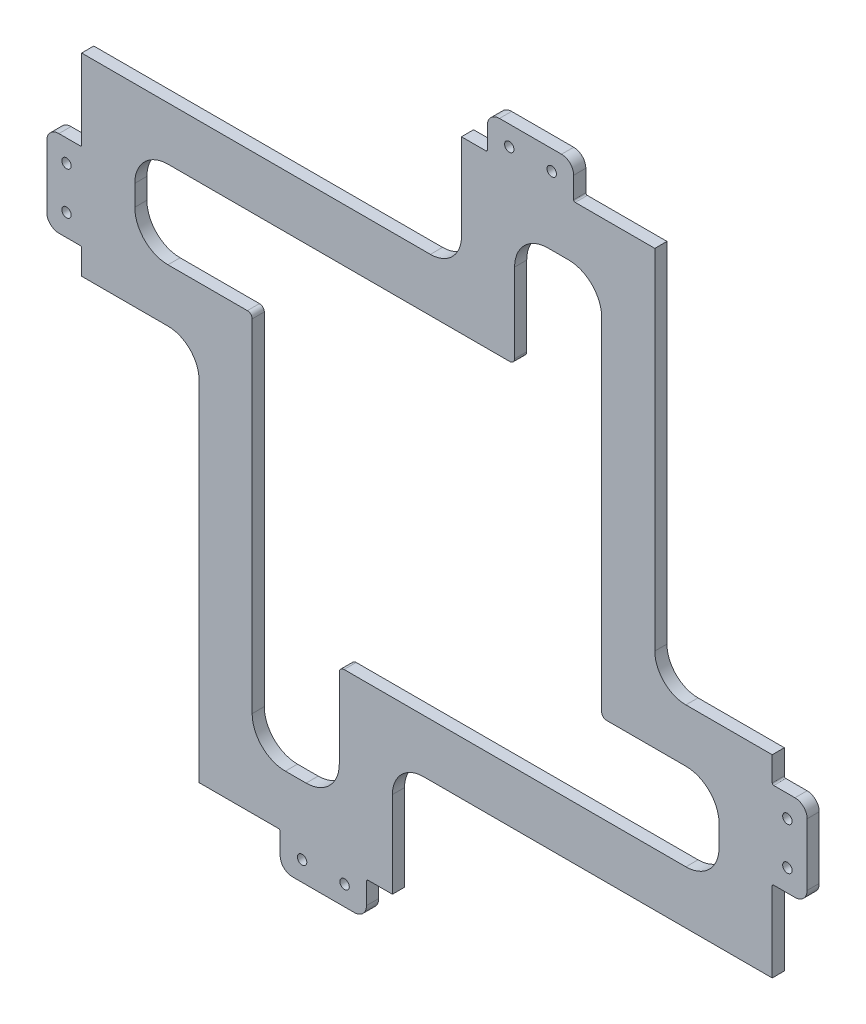
SolidWorks part; units mm, degrees
ref_plane "front" through (0, 0, 0) normal (0, 0, 1) x (1, 0, 0)
ref_plane "top" through (0, 0, 0) normal (0, 1, 0) x (1, 0, 0)
ref_plane "right" through (0, 0, 0) normal (1, 0, 0) x (0, 0, -1)
ref_axis "Axis1" through (0, 0, -69.7337) along (0, 0, 1)
sketch "Sketch1" plane through (0, 0, 0) normal (0, 0, 1) x (1, 0, 0)
  line L0 (-14.4526, 14.4526) -> (14.4526, 14.4526)
  line L1 (14.4526, 14.4526) -> (14.4526, -14.4526)
  line L2 (14.4526, -14.4526) -> (-14.4526, -14.4526)
  line L3 (-14.4526, -14.4526) -> (-14.4526, 14.4526)
  line L4 (-14.4526, 0) -> (-165.194, 0) construction
  line L5 (-165.194, 0) -> (0, 29.1282)
  line L6 (-165.194, 0) -> (0, 14.4526)
  dimension "D1" = 10
  dimension "D2" = 5
  dimension "D3" = 165.194
  dimension "D4" = 167.7424
  dimension "A" = 28.9052
sketch "Sketch2" plane through (0, 0, 0) normal (0, 0, 1) x (1, 0, 0)
  line L0 (-11.5621, 14.4526) -> (6.9372, 14.4526)
  line L1 (-14.4526, 14.4526) -> (14.4526, 14.4526) construction
  line L2 (7.5154, 15.0307) -> (7.5154, 21.6789)
  line L3 (14.4526, 21.6789) -> (14.4526, 5.781)
  line L4 (14.4526, 5.781) -> (19.0774, 5.781)
  line L5 (19.0774, 5.781) -> (19.0774, 28.9052)
  line L6 (4.9314, 28.9052) -> (2.8905, 28.9052)
  line L7 (2.8905, 21.6789) -> (7.5154, 21.6789) construction
  line L8 (2.8905, 28.9052) -> (2.8905, 21.6789)
  line L10 (19.0774, 28.9052) -> (12.4117, 28.9052)
  line L11 (12.2847, 29.0322) -> (12.2847, 30.8102)
  line L12 (11.2687, 31.8262) -> (6.0744, 31.8262)
  line L13 (5.0584, 30.8102) -> (5.0584, 29.0322)
  line L14 (0.2891, 19.0774) -> (-11.5621, 19.0774)
  line L15 (-11.5621, 19.0774) -> (-11.5621, 14.4526)
  line L16 (14.4526, 14.4526) -> (14.4526, -14.4526) construction
  line L18 (10.1168, 24.2804) -> (11.8511, 24.2804)
  arc A0 (2.8905, 21.6789) -> (0.2891, 19.0774) centre (0.2891, 21.6789) cw
  arc A1 (6.0744, 31.8262) -> (5.0584, 30.8102) centre (6.0744, 30.8102) ccw
  arc A2 (12.2847, 30.8102) -> (11.2687, 31.8262) centre (11.2687, 30.8102) ccw
  arc A3 (5.0584, 29.0322) -> (4.9314, 28.9052) centre (4.9314, 29.0322) cw
  circle A4 centre (6.8936, 30.1752) radius 0.3937
  arc A5 (12.4117, 28.9052) -> (12.2847, 29.0322) centre (12.4117, 29.0322) cw
  circle A6 centre (10.4496, 30.1752) radius 0.3937
  arc A9 (11.8511, 24.2804) -> (14.4526, 21.6789) centre (11.8511, 21.6789) cw
  arc A10 (7.5154, 21.6789) -> (10.1168, 24.2804) centre (10.1168, 21.6789) cw
  arc A11 (6.9372, 14.4526) -> (7.5154, 15.0307) centre (6.9372, 15.0307) ccw
  point P16 (8.6716, 31.8262)
  dimension "D9" = 0.5781
  dimension "D6" = 0.127
  dimension "D2" = 14.4526
  dimension "D5" = 7.2263
  dimension "D8" = 4.6248
  dimension "D10" = 4.6248
  dimension "D12" = 11.5621
  dimension "D13" = 5.781
  dimension "D4" = 2.8905
  dimension "D15" = 16.1869
  dimension "D11" = 8.6716
  dimension "D17" = 1.778
extrude "Extrude1" add sketch "Sketch2" against normal mid plane 1.016
pattern_circular "CirPattern1" count 4 over 360 about axis through (0, 0, -69.7337) along (0, 0, 1) of "Extrude1"
sketch "Sketch4" plane through (0, 0, 0.508) normal (0, 0, 1) x (1, 0, 0)
  line L172 (-11.8511, -24.4582) -> (-10.1168, -24.4582)
  line L173 (-7.3376, -21.6789) -> (-7.3376, -15.0307)
  line L174 (-6.9372, -14.6304) -> (21.6789, -14.6304)
  line L175 (24.4582, -11.8511) -> (24.4582, -10.1168)
  line L176 (21.6789, -7.3376) -> (15.0307, -7.3376)
  line L177 (14.6304, -6.9372) -> (14.6304, 21.6789)
  line L178 (11.8511, 24.4582) -> (10.1168, 24.4582)
  line L179 (7.3376, 21.6789) -> (7.3376, 15.0307)
  line L180 (6.9372, 14.6304) -> (-21.6789, 14.6304)
  line L181 (-24.4582, 11.8511) -> (-24.4582, 10.1168)
  line L182 (-21.6789, 7.3376) -> (-15.0307, 7.3376)
  line L183 (-14.6304, 6.9372) -> (-14.6304, -21.6789)
  line L184 (-11.8511, -24.4582) -> (-10.1168, -24.4582)
  line L185 (-7.3376, -21.6789) -> (-7.3376, -15.0307)
  line L186 (-6.9372, -14.6304) -> (21.6789, -14.6304)
  line L187 (24.4582, -11.8511) -> (24.4582, -10.1168)
  line L188 (21.6789, -7.3376) -> (15.0307, -7.3376)
  line L189 (14.6304, -6.9372) -> (14.6304, 21.6789)
  line L190 (11.8511, 24.4582) -> (10.1168, 24.4582)
  line L191 (7.3376, 21.6789) -> (7.3376, 15.0307)
  line L192 (6.9372, 14.6304) -> (-21.6789, 14.6304)
  line L193 (-24.4582, 11.8511) -> (-24.4582, 10.1168)
  line L194 (-21.6789, 7.3376) -> (-15.0307, 7.3376)
  line L195 (-14.6304, 6.9372) -> (-14.6304, -21.6789)
  arc A157 (-14.6304, -21.6789) -> (-11.8511, -24.4582) centre (-11.8511, -21.6789) ccw
  arc A158 (-10.1168, -24.4582) -> (-7.3376, -21.6789) centre (-10.1168, -21.6789) ccw
  arc A159 (-6.9372, -14.6304) -> (-7.3376, -15.0307) centre (-6.9372, -15.0307) ccw
  arc A160 (21.6789, -14.6304) -> (24.4582, -11.8511) centre (21.6789, -11.8511) ccw
  arc A161 (24.4582, -10.1168) -> (21.6789, -7.3376) centre (21.6789, -10.1168) ccw
  arc A162 (14.6304, -6.9372) -> (15.0307, -7.3376) centre (15.0307, -6.9372) ccw
  arc A163 (14.6304, 21.6789) -> (11.8511, 24.4582) centre (11.8511, 21.6789) ccw
  arc A164 (10.1168, 24.4582) -> (7.3376, 21.6789) centre (10.1168, 21.6789) ccw
  arc A165 (6.9372, 14.6304) -> (7.3376, 15.0307) centre (6.9372, 15.0307) ccw
  arc A166 (-21.6789, 14.6304) -> (-24.4582, 11.8511) centre (-21.6789, 11.8511) ccw
  arc A167 (-24.4582, 10.1168) -> (-21.6789, 7.3376) centre (-21.6789, 10.1168) ccw
  arc A168 (-14.6304, 6.9372) -> (-15.0307, 7.3376) centre (-15.0307, 6.9372) ccw
  arc A169 (-14.6304, -21.6789) -> (-11.8511, -24.4582) centre (-11.8511, -21.6789) ccw
  arc A170 (-10.1168, -24.4582) -> (-7.3376, -21.6789) centre (-10.1168, -21.6789) ccw
  arc A171 (-6.9372, -14.6304) -> (-7.3376, -15.0307) centre (-6.9372, -15.0307) ccw
  arc A172 (21.6789, -14.6304) -> (24.4582, -11.8511) centre (21.6789, -11.8511) ccw
  arc A173 (24.4582, -10.1168) -> (21.6789, -7.3376) centre (21.6789, -10.1168) ccw
  arc A174 (14.6304, -6.9372) -> (15.0307, -7.3376) centre (15.0307, -6.9372) ccw
  arc A175 (14.6304, 21.6789) -> (11.8511, 24.4582) centre (11.8511, 21.6789) ccw
  arc A176 (10.1168, 24.4582) -> (7.3376, 21.6789) centre (10.1168, 21.6789) ccw
  arc A177 (6.9372, 14.6304) -> (7.3376, 15.0307) centre (6.9372, 15.0307) ccw
  arc A178 (-21.6789, 14.6304) -> (-24.4582, 11.8511) centre (-21.6789, 11.8511) ccw
  arc A179 (-24.4582, 10.1168) -> (-21.6789, 7.3376) centre (-21.6789, 10.1168) ccw
  arc A180 (-14.6304, 6.9372) -> (-15.0307, 7.3376) centre (-15.0307, 6.9372) ccw
  dimension "D1" = 0.1778
extrude "Cut-Extrude1" cut sketch "Sketch4" against normal blind 1.27
equation "\"D2@Sketch2\" = .5 * \"A\""
equation "\"D13@Sketch2\" = .2 * \"A\""
equation "\"D8@Sketch2\" = .16 * \"A\""
equation "\"D10@Sketch2\" = .16 * \"A\""
equation "\"D5@Sketch2\" = .25 * \"A\""
equation "\"D12@Sketch2\" = .4 * \"A\""
equation "\"D4@Sketch2\"=.1*\"A\""
equation "\"D9@Sketch2\"=.02*\"A\""
equation "\"D11@Sketch2\"=.3*\"A\""
